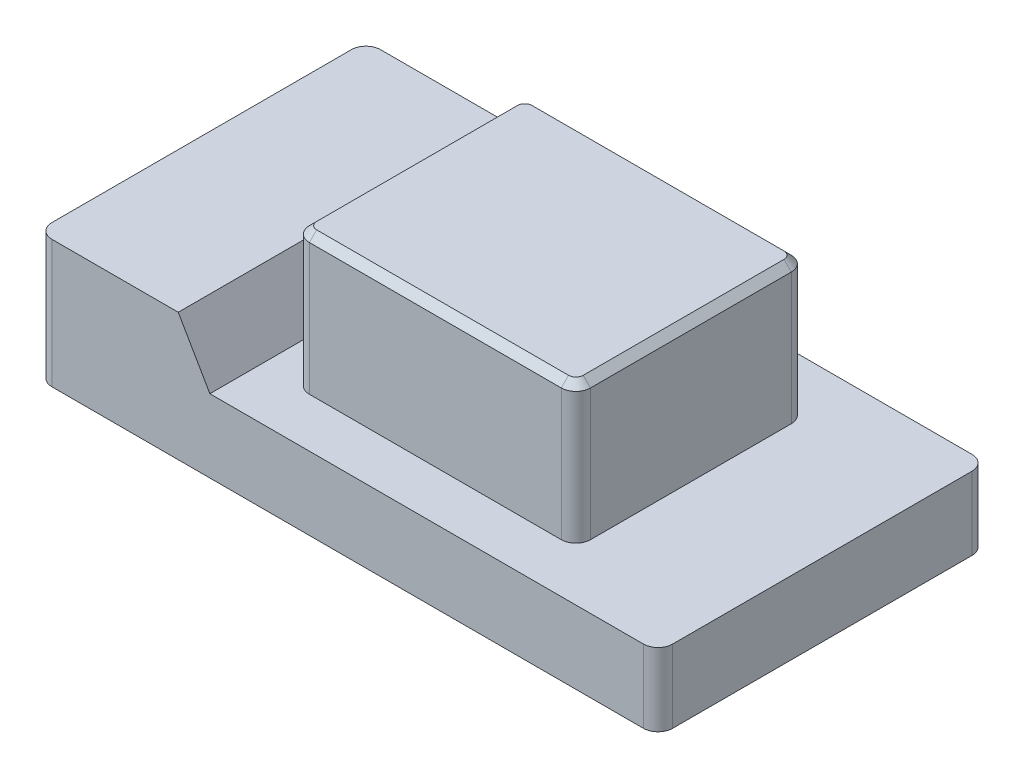
SolidWorks part; units mm, degrees
ref_plane "前视基准面" through (0, 0, 0) normal (0, 0, 1) x (1, 0, 0)
ref_plane "上视基准面" through (0, 0, 0) normal (0, 1, 0) x (1, 0, 0)
ref_plane "右视基准面" through (0, 0, 0) normal (1, 0, 0) x (0, 0, -1)
other "Configuration Table"
sketch "草图1" plane through (0, 0, 0) normal (0, 1, 0) x (1, 0, 0)
  line L1 (42.5, -22.5) -> (-42.5, -22.5)
  line L2 (42.5, -22.5) -> (42.5, 22.5)
  line L3 (42.5, 22.5) -> (-42.5, 22.5)
  line L4 (-42.5, -22.5) -> (-42.5, 22.5)
  line L5 (42.5, -22.5) -> (-42.5, 22.5) construction
  line L6 (42.5, 22.5) -> (-42.5, -22.5) construction
  point P0 (0, 0)
  dimension "D1" = 45
  dimension "D2" = 85
extrude "凸台-拉伸1" add sketch "草图1" along normal blind 10
sketch "草图2" plane through (0, 10, 0) normal (0, 1, 0) x (1, 0, 0)
  line L0 (-42.5, -22.5) -> (42.5, -22.5) construction
  line L1 (-42.5, 22.5) -> (-23.5, 22.5)
  line L2 (-42.5, 22.5) -> (-42.5, -22.5)
  line L3 (-42.5, -22.5) -> (-23.5, -22.5)
  line L4 (-23.5, 22.5) -> (-23.5, -22.5)
  dimension "D1" = 19
extrude "凸台-拉伸2" add sketch "草图2" along normal blind 7.5
chamfer "倒角1" distance 8 angle 30 1 edges at (-23.5, 10, 0) first distance on face at (-23.5, 13.75, 0)
sketch "草图3" plane through (0, 10, 0) normal (0, 1, 0) x (1, 0, 0)
  line L0 (42.5, -22.5) -> (42.5, 22.5) construction
  line L1 (24.5, -15.75) -> (-14, -15.75)
  line L2 (24.5, -15.75) -> (24.5, 15.75)
  line L3 (24.5, 15.75) -> (-14, 15.75)
  line L4 (-14, -15.75) -> (-14, 15.75)
  line L5 (24.5, -15.75) -> (-14, 15.75) construction
  line L6 (24.5, 15.75) -> (-14, -15.75) construction
  point P0 (5.25, 0)
  point P7 (0, 0)
  dimension "D1" = 18
  dimension "D2" = 38.5
  dimension "D3" = 31.5
extrude "凸台-拉伸3" add sketch "草图3" along normal blind 19
fillet "圆角1" radius 2 4 edges at (-14, 19.5, -15.75) (24.5, 19.5, -15.75) (24.5, 19.5, 15.75) (-14, 19.5, 15.75)
chamfer "倒角2" distance 1 angle 45 8 edges at (5.25, 29, -15.75) (-13.4142, 29, -15.1642) (23.9142, 29, -15.1642) (-14, 29, 0) (24.5, 29, 0) (-13.4142, 29, 15.1642) (23.9142, 29, 15.1642) (5.25, 29, 15.75)
fillet "圆角2" radius 2 4 edges at (-42.5, 8.75, -22.5) (42.5, 5, -22.5) (42.5, 5, 22.5) (-42.5, 8.75, 22.5)
